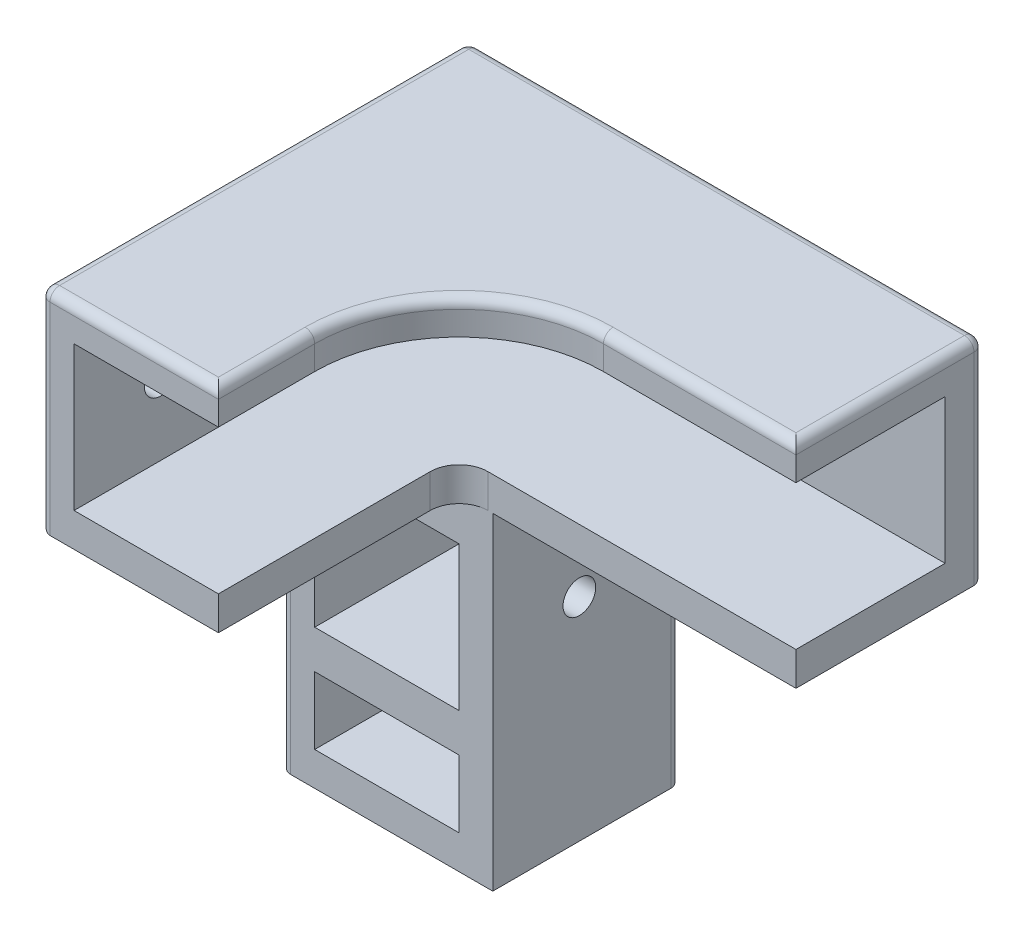
SolidWorks part; units mm, degrees
ref_plane "Front Plane" through (0, 0, 0) normal (0, 0, 1) x (1, 0, 0)
ref_plane "Top Plane" through (0, 0, 0) normal (0, 1, 0) x (1, 0, 0)
ref_plane "Right Plane" through (0, 0, 0) normal (1, 0, 0) x (0, 0, -1)
sketch "Sketch1" plane through (0, 0, 0) normal (0, 0, 1) x (1, 0, 0)
  line L1 (-5.6994, 32.9163) -> (16.3006, 32.9163)
  line L2 (-5.6994, 10.9163) -> (-5.6994, -23.0837)
  line L3 (-5.6994, -23.0837) -> (16.3006, -23.0837)
  line L4 (16.3006, 32.9163) -> (16.3006, -23.0837)
  line L5 (-5.6994, 10.9163) -> (-37.1994, 10.9163)
  line L7 (-5.6994, 32.9163) -> (-37.1994, 32.9163)
  line L8 (-37.1994, 10.9163) -> (-37.1994, 32.9163)
  dimension "D1" = 22
  dimension "D2" = 22
  dimension "D3" = 56
  dimension "D4" = 53.5
extrude "Boss-Extrude1" add sketch "Sketch1" along normal blind 19.5
sketch "Sketch3" plane through (0, 0, 19.5) normal (0, 0, 1) x (1, 0, 0)
  line L1 (16.3006, 32.9163) -> (-2.1994, 32.9163)
  line L2 (16.3006, 32.9163) -> (16.3006, 10.9163)
  line L3 (16.3006, 10.9163) -> (-2.1994, 10.9163)
  line L4 (-2.1994, 32.9163) -> (-2.1994, 10.9163)
  dimension "D1" = 18.5
extrude "Boss-Extrude2" add sketch "Sketch3" along normal blind 25
sketch "Sketch5" plane through (0, 0, 44.5) normal (0, 0, 1) x (1, 0, 0)
  line L0 (-37.1994, 32.9163) -> (-37.1994, 10.9163) construction
  line L1 (-37.1994, 29.4163) -> (12.8006, 29.4163)
  line L2 (-37.1994, 29.4163) -> (-37.1994, 14.4163)
  line L3 (-37.1994, 14.4163) -> (12.8006, 14.4163)
  line L4 (12.8006, 29.4163) -> (12.8006, 14.4163)
  line L5 (16.3006, 10.9163) -> (16.3006, 32.9163) construction
  line L6 (-2.1994, 6.4163) -> (12.8006, 6.4163)
  line L7 (-2.1994, 6.4163) -> (-2.1994, -8.5837)
  line L8 (-2.1994, -8.5837) -> (12.8006, -8.5837)
  line L9 (12.8006, 6.4163) -> (12.8006, -8.5837)
  line L12 (-2.1994, 32.9163) -> (-37.1994, 32.9163) construction
  line L13 (-2.1994, 10.9163) -> (16.3006, 10.9163) construction
  line L15 (16.3006, -23.0837) -> (16.3006, 10.9163) construction
  line L16 (-5.6994, -23.0837) -> (16.3006, -23.0837) construction
  line L17 (-2.1994, -12.5837) -> (12.8006, -12.5837)
  line L18 (-2.1994, -12.5837) -> (-2.1994, -19.5837)
  line L19 (-2.1994, -19.5837) -> (12.8006, -19.5837)
  line L20 (12.8006, -12.5837) -> (12.8006, -19.5837)
  dimension "D1" = 3.5
  dimension "D2" = 4.5
  dimension "D3" = 15
  dimension "D4" = 3.5
  dimension "D5" = 15
  dimension "D6" = 15
  dimension "D7" = 3.5
  dimension "D8" = 15
  dimension "D9" = 4
  dimension "D10" = 3.5
extrude "Cut-Extrude1" cut sketch "Sketch5" against normal offset from surface (40.5 mm away) 4 up to face at (-8.8661, 6.9163, 0)
sketch "Sketch7" plane through (16.3006, 0, 0) normal (1, 0, 0) x (0, 0, -1)
  line L0 (-34.5, 10.9163) -> (-19.5, 10.9163)
  line L1 (-44.5, 10.9163) -> (-19.5, 10.9163) construction
  line L2 (-19.5, 10.9163) -> (-19.5, -4.0837)
  line L3 (-19.5, -23.0837) -> (-19.5, 10.9163) construction
  arc A0 (-34.5, 10.9163) -> (-19.5, -4.0837) centre (-34.5, -4.0837) cw
  dimension "D1" = 15
extrude "Boss-Extrude4" add sketch "Sketch7" against normal blind 3.5
sketch "Sketch8" plane through (0, 0, 0) normal (0, 0, -1) x (-1, 0, 0)
  line L0 (5.6994, 10.9163) -> (20.6994, 10.9163)
  line L1 (37.1994, 10.9163) -> (5.6994, 10.9163) construction
  line L2 (5.6994, 10.9163) -> (5.6994, -4.0837)
  line L3 (5.6994, 10.9163) -> (5.6994, -23.0837) construction
  arc A0 (20.6994, 10.9163) -> (5.6994, -4.0837) centre (20.6994, -4.0837) ccw
  dimension "D1" = 15
extrude "Boss-Extrude5" add sketch "Sketch8" against normal blind 3.5
sketch "Sketch9" plane through (0, 32.9163, 0) normal (0, 1, 0) x (1, 0, 0)
  line L0 (-2.1994, -34.5) -> (-2.1994, -19.5)
  line L1 (-2.1994, -44.5) -> (-2.1994, -19.5) construction
  line L2 (-2.1994, -19.5) -> (-17.1994, -19.5)
  line L3 (-2.1994, -19.5) -> (-37.1994, -19.5) construction
  arc A0 (-2.1994, -34.5) -> (-17.1994, -19.5) centre (-17.1994, -34.5) ccw
  dimension "D1" = 15
extrude "Boss-Extrude6" add sketch "Sketch9" against normal blind 3.5
fillet "Fillet3" radius 3 1 edges
sketch "Sketch11" plane through (0, 0, 0) normal (0, 0, -1) x (-1, 0, 0)
  line L0 (1.1994, -23.0837) -> (1.1994, 10.9163) construction
  line L2 (5.6994, -23.0837) -> (-16.3006, -23.0837) construction
  line L5 (5.6994, -4.0837) -> (5.6994, -23.0837) construction
  text T0 "MR.3" font "Century Gothic" height 12
  dimension "D1" = 4.5
extrude "Cut-Extrude3" cut sketch "Sketch11" against normal blind 1
sketch "Sketch12" plane through (0, 0, 0) normal (0, 0, -1) x (-1, 0, 0)
  line L0 (37.1994, 21.9163) -> (-16.3006, 21.9163) construction
  line L1 (37.1994, 32.9163) -> (37.1994, 10.9163) construction
  line L2 (-16.3006, -23.0837) -> (-16.3006, 32.9163) construction
  line L3 (-12.8006, 14.4163) -> (-12.8006, 29.4163) construction
  circle A0 centre (-5.3006, 21.9163) radius 1.7
  circle A1 centre (10.9494, 21.9163) radius 1.7
  circle A2 centre (27.1994, 21.9163) radius 1.7
  dimension "D4" = 3.4
  dimension "D1" = 7.5
  dimension "D2" = 10
  dimension "D3" = 16.25
extrude "Cut-Extrude4" cut sketch "Sketch12" against normal blind 5
sketch "Sketch13" plane through (-5.6994, 0, 0) normal (-1, 0, 0) x (0, 0, 1)
  line L0 (4, 6.4163) -> (19.5, 6.4163) construction
  line L1 (19.5, 10.9163) -> (19.5, -23.0837) construction
  circle A0 centre (10.5, -1.0837) radius 1.7
  dimension "D2" = 9
  dimension "D3" = 3.4
  dimension "D1" = 7.5
extrude "Cut-Extrude5" cut sketch "Sketch13" against normal blind 45
sketch "Sketch14" plane through (16.3006, 0, 0) normal (1, 0, 0) x (0, 0, -1)
  line L0 (-10.5, -1.0837) -> (-10.5, 32.9163) construction
  line L1 (-44.5, 32.9163) -> (0, 32.9163) construction
  line L2 (-44.5, 21.9163) -> (-10.5, 21.9163) construction
  line L3 (-44.5, 10.9163) -> (-44.5, 32.9163) construction
  circle A0 centre (-10.5, 21.9163) radius 1.7
  circle A1 centre (-35.5, 21.9163) radius 1.7
  dimension "D1" = 3.4
  dimension "D2" = 9
extrude "Cut-Extrude6" cut sketch "Sketch14" against normal blind 45
sketch "Sketch15" plane through (0, -23.0837, 0) normal (0, -1, 0) x (1, 0, 0)
  line L0 (16.3006, 9.75) -> (-5.6994, 9.75) construction
  line L1 (16.3006, 19.5) -> (16.3006, 0) construction
  line L2 (-5.6994, 19.5) -> (-5.6994, 0) construction
  line L3 (5.3006, 19.5) -> (5.3006, 0) construction
  line L4 (-5.6994, 19.5) -> (16.3006, 19.5) construction
  line L5 (-5.6994, 0) -> (16.3006, 0) construction
  circle A0 centre (5.3006, 9.75) radius 1.7
  dimension "D1" = 3.4
extrude "Cut-Extrude7" cut sketch "Sketch15" against normal blind 4
mirror "Mirror2" about plane through (16.3006, 32.9163, 19.5) normal (-1, 0, 0) of "Cut-Extrude7", "Cut-Extrude6", "Cut-Extrude5", "Cut-Extrude4", "Fillet3", "Boss-Extrude6", "Boss-Extrude5", "Boss-Extrude4", "Cut-Extrude1", "Boss-Extrude2", "Boss-Extrude1"
sketch "Sketch16" plane through (0, 0, 0) normal (0, 0, -1) x (-1, 0, 0)
  line L0 (-69.8006, 32.9163) -> (37.1994, 32.9163) construction
  line L1 (-16.3006, 32.9163) -> (53.9943, 32.9163)
  line L2 (-16.3006, 32.9163) -> (-16.3006, -24.95)
  line L3 (-16.3006, -24.95) -> (53.9943, -24.95)
  line L4 (53.9943, 32.9163) -> (53.9943, -24.95)
extrude "Cut-Extrude8" cut sketch "Sketch16" against normal blind 72
sketch "Sketch20" plane through (0, 0, 0) normal (0, 0, -1) x (-1, 0, 0)
  line L0 (-20.8006, -23.0837) -> (-20.8006, 10.9163) construction
  line L1 (-16.3006, -23.0837) -> (-38.3006, -23.0837) construction
  line L2 (-16.3006, 32.9163) -> (-16.3006, -23.0837) construction
  text T0 "MR.3" font "Century Gothic" height 12
  dimension "D1" = 4.5
extrude "Cut-Extrude9" cut sketch "Sketch20" against normal blind 1
fillet "Fillet4" radius 1 16 edges at (16.3006, 10.9163, 39.5) (16.3006, 6.5229, 23.8934) (61.5506, 10.9163, 0) (42.694, 6.5229, 0) (34.8006, 32.9163, 39.5) (39.194, 32.9163, 23.8934) (16.3006, -13.5837, 19.5) (38.3006, -13.5837, 0) (16.3006, 4.9163, 0) (43.0506, 32.9163, 0) (16.3006, 32.9163, 22.25) (16.3006, 21.9163, 44.5) (69.8006, 21.9163, 0) (69.8006, 32.9163, 9.75) (25.5506, 32.9163, 44.5)
